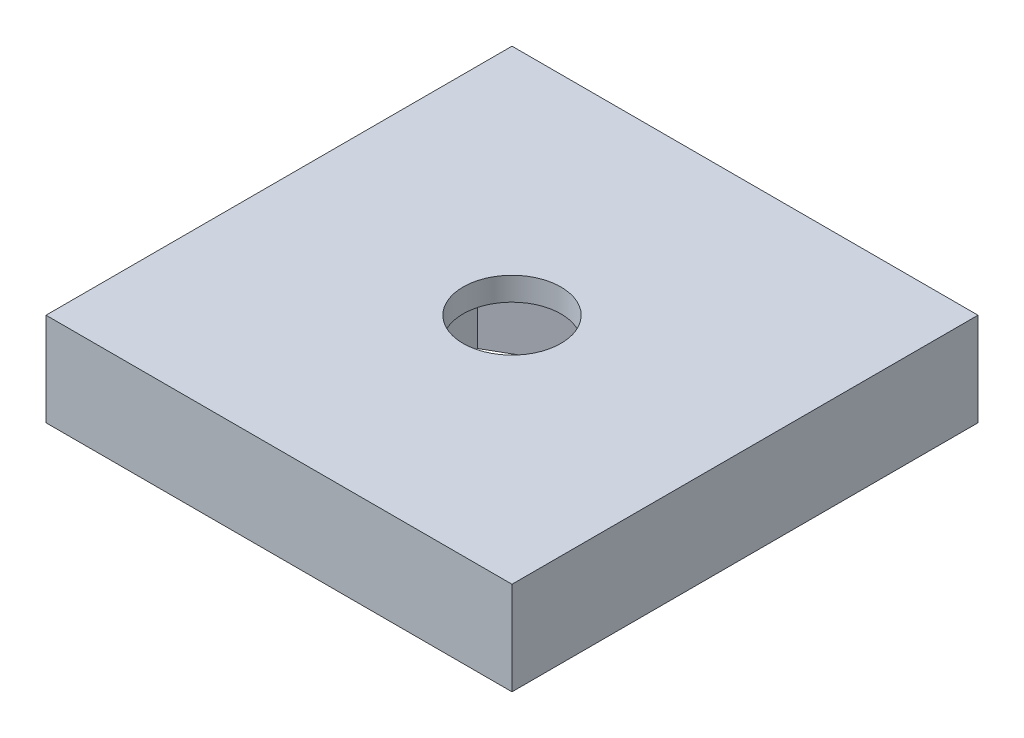
SolidWorks part; units mm, degrees
ref_plane "Front" through (0, 0, 0) normal (0, 0, 1) x (1, 0, 0)
ref_plane "Top" through (0, 0, 0) normal (0, 1, 0) x (1, 0, 0)
ref_plane "Right" through (0, 0, 0) normal (1, 0, 0) x (0, 0, -1)
sketch "Sketch1" plane through (0, 0, 0) normal (0, 1, 0) x (1, 0, 0)
  line L1 (0, 4.0415) -> (-3.5, 2.0207)
  line L2 (-3.5, 2.0207) -> (-3.5, -2.0207)
  line L3 (-3.5, -2.0207) -> (0, -4.0415)
  line L4 (0, -4.0415) -> (3.5, -2.0207)
  line L5 (3.5, -2.0207) -> (3.5, 2.0207)
  line L6 (3.5, 2.0207) -> (0, 4.0415)
  line L7 (-10, -10) -> (10, -10)
  line L8 (-10, -10) -> (-10, 10)
  line L9 (-10, 10) -> (10, 10)
  line L10 (10, -10) -> (10, 10)
  line L11 (-10, -10) -> (10, 10) construction
  line L12 (-10, 10) -> (10, -10) construction
  circle A0 centre (0, 0) radius 3.5 construction
  circle A1 centre (0, 0) radius 2.1
  point P14 (0, 4.0415)
  dimension "D2" = 4.2
  dimension "D1" = 7
  dimension "D3" = 20
extrude "Boss-Extrude1" add sketch "Sketch1" along normal blind 4 contours L7 L10 L9 L8
extrude "Cut-Extrude1" cut sketch "Sketch1<3>" along normal blind 3 contours L4 L5 L6 L1 L2 L3
sketch "Sketch1<3>" plane through (0, 0, 0) normal (0, 1, 0) x (1, 0, 0) same geometry as "Sketch1"
extrude "Cut-Extrude2" cut sketch "Sketch1<4>" along normal through all both and the other way through all contours A1 region at (0, 0, 0)
sketch "Sketch1<4>" plane through (0, 0, 0) normal (0, 1, 0) x (1, 0, 0) same geometry as "Sketch1"
